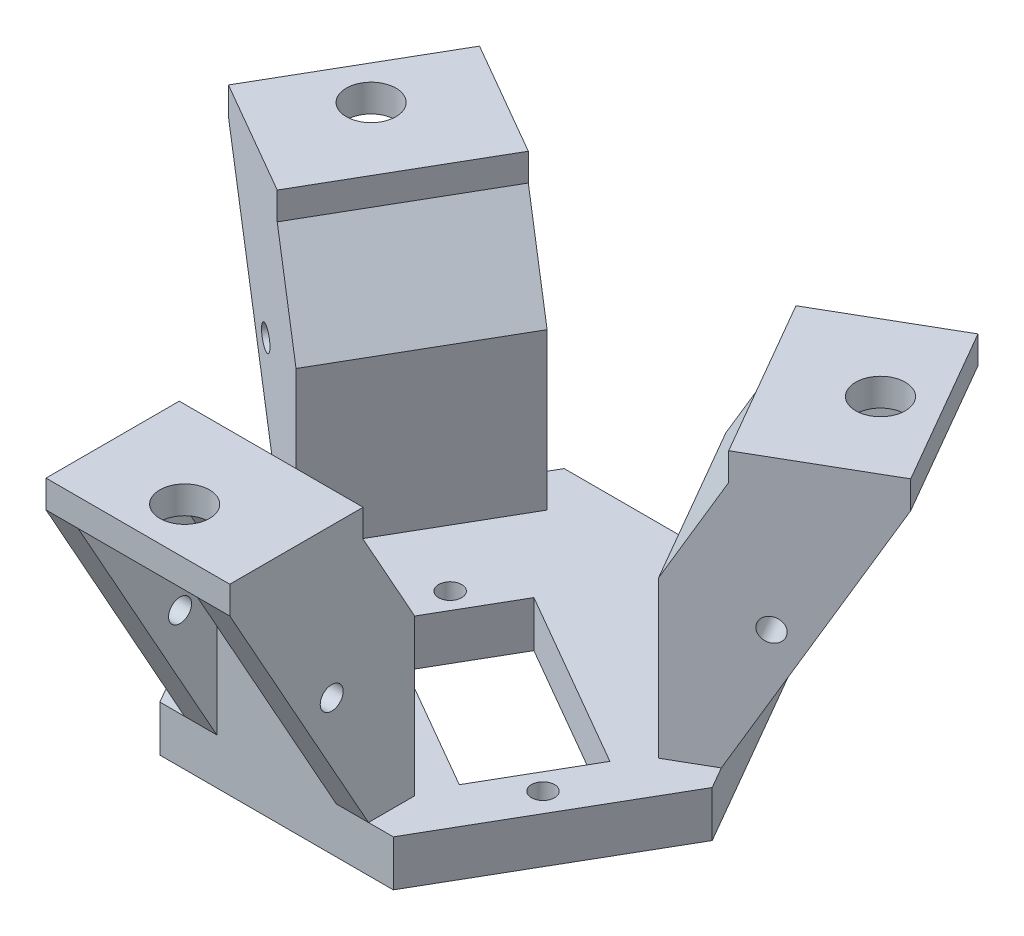
SolidWorks part; units mm, degrees
ref_plane "Front Plane" through (0, 0, 0) normal (0, 0, 1) x (1, 0, 0)
ref_plane "Top Plane" through (0, 0, 0) normal (0, 1, 0) x (1, 0, 0)
ref_plane "Right Plane" through (0, 0, 0) normal (1, 0, 0) x (0, 0, -1)
sketch "Sketch1" plane through (0, 0, 0) normal (0, 1, 0) x (1, 0, 0)
  line L0 (25.4034, 0) -> (12.7017, 22)
  line L1 (12.7017, 22) -> (-12.7017, 22)
  line L2 (-12.7017, 22) -> (-25.4034, 0)
  line L3 (-25.4034, 0) -> (-12.7017, -22)
  line L4 (-12.7017, -22) -> (12.7017, -22)
  line L5 (12.7017, -22) -> (25.4034, 0)
  circle A0 centre (0, 0) radius 25.4034 construction
  dimension "D1" = 22
extrude "Boss-Extrude1" add sketch "Sketch1" along normal blind 5
sketch "Sketch4" plane through (0, 5, 0) normal (0, 1, 0) x (1, 0, 0)
  line L0 (-12.7017, -22) -> (12.7017, -22) construction
  line L1 (-10, -22) -> (10, -22)
  line L2 (-10, -22) -> (-10, -17)
  line L3 (-10, -17) -> (10, -17)
  line L4 (10, -22) -> (10, -17)
  point P6 (0, -22)
  point P7 (0, -22)
  dimension "D1" = 20
  dimension "D2" = 5
extrude "Boss-Extrude3" add sketch "Sketch4" along normal blind 17
sketch "Sketch2" plane through (0, 0, 0) normal (1, 0, 0) x (0, 0, -1)
  line L1 (-22, 5) -> (-22, 0) construction
  line L3 (-22, 22) -> (-22, 5)
  line L5 (-22, 5) -> (-31.5, 22)
  line L7 (-31.5, 22) -> (-22, 22)
  line L8 (-22, 22) -> (-17, 22) construction
  circle A1 centre (-26, 18.75) radius 1.25
  dimension "D1" = 2.5
  dimension "D2" = 4
  dimension "D3" = 9.5
  dimension "D4" = 3.25
extrude "Boss-Extrude2" add sketch "Sketch2" along normal up to surface (10 mm away) from offset 6.5 up to face at (10, 13.5, 19.5)
mirror "Mirror1" about plane through (0, 0, 0) normal (1, 0, 0) of "Boss-Extrude3", "Boss-Extrude2"
sketch "Sketch5" plane through (0, 0, 0) normal (0, 0, 1) x (1, 0, 0)
  line L0 (0, 0) -> (0, 15.7855) construction
pattern_circular "CirPattern1" count 3 over 360 about axis through (0, 0, 0) along (0, 1, 0) of "Mirror1", "Boss-Extrude3", "Boss-Extrude2" reverse direction yes
sketch "Sketch3" plane through (0, 5, 0) normal (0, 1, 0) x (1, 0, 0)
  line L0 (-5.1962, 3) -> (0, 0) construction
  line L1 (-2.1962, 8.1962) -> (17.376, -3.1038)
  line L2 (-2.1962, 8.1962) -> (-8.1962, -2.1962)
  line L3 (-8.1962, -2.1962) -> (11.376, -13.4962)
  line L4 (17.376, -3.1038) -> (11.376, -13.4962)
  line L5 (12.7017, -22) -> (25.4034, 0) construction
  point P7 (-5.1962, 3)
  dimension "D1" = 22.6
  dimension "D2" = 12
  dimension "D3" = 6
extrude "Cut-Extrude1" cut sketch "Sketch3" against normal up to next
sketch "Sketch6" plane through (0, 5, 0) normal (0, 1, 0) x (1, 0, 0)
  line L0 (-2.1962, 8.1962) -> (-8.1962, -2.1962) construction
  line L1 (11.376, -13.4962) -> (17.376, -3.1038) construction
  line L2 (-7.3612, 4.25) -> (16.5411, -9.55) construction
  circle A0 centre (-7.3612, 4.25) radius 1.25
  circle A1 centre (16.5411, -9.55) radius 1.25
  point P8 (14.376, -8.3)
  point P9 (-5.1962, 3)
  dimension "D3" = 2.5
  dimension "D1" = 2.5
  dimension "D2" = 2.5
extrude "Cut-Extrude2" cut sketch "Sketch6" against normal up to next
sketch "Sketch10" plane through (0, 22, 0) normal (0, 1, 0) x (1, 0, 0)
  line L0 (-22.2798, 24.4103) -> (-9.7224, 17.1603)
  line L1 (-9.7224, 17.1603) -> (-19.7224, -0.1603)
  line L2 (-19.7224, -0.1603) -> (-32.2798, 7.0897)
  line L3 (-32.2798, 7.0897) -> (-30.5298, 10.1208)
  line L4 (-30.5298, 10.1208) -> (-22.3026, 5.3708)
  line L5 (-22.3026, 5.3708) -> (-15.8026, 16.6292)
  line L6 (-15.8026, 16.6292) -> (-24.0298, 21.3792)
  line L7 (-24.0298, 21.3792) -> (-22.2798, 24.4103)
sketch "Sketch11" plane through (-5, 0, 8.6603) normal (-0.5, 0, 0.866) x (0.866, 0, 0.5)
  line L0 (-31.5, 22) -> (-37.0882, 32)
  line L1 (-22, 5) -> (-31.5, 22) construction
  dimension "D1" = 10
sweep "Sweep1" add profiles "Sketch10" path "Sketch11"
sketch "Sketch12" plane through (0, 32, 0) normal (0, 1, 0) x (1, 0, 0)
  line L0 (-27.1194, 27.2044) -> (-14.562, 19.9544)
  line L1 (-27.1194, 27.2044) -> (-37.1194, 9.8839)
  line L2 (-14.562, 19.9544) -> (-24.562, 2.6339)
  line L3 (-37.1194, 9.8839) -> (-24.562, 2.6339)
  line L4 (-37.1194, 9.8839) -> (-24.562, 2.6339) construction
extrude "Boss-Extrude4" add sketch "Sketch12" along normal blind 3
sketch "Sketch13" plane through (0, 35, 0) normal (0, 1, 0) x (1, 0, 0)
  line L0 (-27.7128, 16) -> (0, 0) construction
  line L1 (-24.562, 2.6339) -> (-14.562, 19.9544) construction
  circle A0 centre (-27.7128, 16) radius 2.7
  point P7 (-19.562, 11.2941)
  dimension "D1" = 5.4
  dimension "D2" = 32
extrude "Cut-Extrude3" cut sketch "Sketch13" against normal up to next
pattern_circular "CirPattern2" count 3 over 360 about axis through (0, 0, 0) along (0, 1, 0) of "Sweep1", "Boss-Extrude4", "Cut-Extrude3" reverse direction yes
